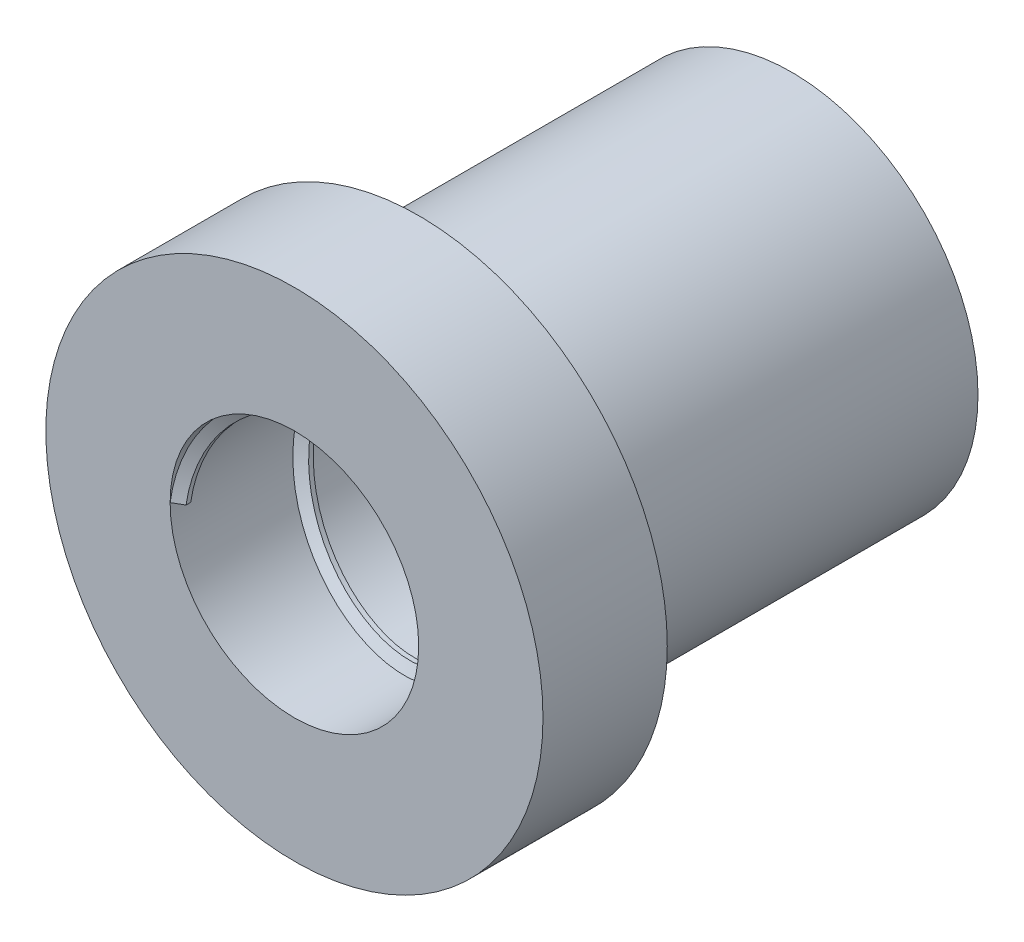
SolidWorks part; units mm, degrees
material "5052-H32"
ref_plane "Front Plane" through (0, 0, 0) normal (0, 0, 1) x (1, 0, 0)
ref_plane "Top Plane" through (0, 0, 0) normal (0, 1, 0) x (1, 0, 0)
ref_plane "Right Plane" through (0, 0, 0) normal (1, 0, 0) x (0, 0, -1)
sketch "Sketch1" plane through (0, 0, 0) normal (0, 0, 1) x (1, 0, 0)
  circle A0 centre (0, 0) radius 15
  circle A1 centre (0, 0) radius 10
  dimension "D1" = 30
  dimension "D2" = 20
extrude "Boss-Extrude1" add sketch "Sketch1" along normal blind 30
sketch "Sketch2" plane through (0, 0, 30) normal (0, 0, 1) x (1, 0, 0)
  circle A0 centre (0, 0) radius 20
  circle A1 centre (0, 0) radius 10
  dimension "D1" = 20
  dimension "D2" = 40
extrude "Boss-Extrude2" add sketch "Sketch2" along normal blind 10
thread "Thread1" pitch 1.5 method extrude profile "Thread Profile1" start angle 0, offset 0, length 40, pitch 10, diameter 20
ref_plane "Plane1" through (-10, 0, 40) normal (0, -1, 0) x (-1, 0, 0)
sketch "Thread Profile1" plane through (-10, 0, 40) normal (0, -1, 0) x (-1, 0, 0)
  line L0 (0, 0) -> (0, 1.5) construction
  line L11 (0, 0) -> (0, 1.3125)
  line L12 (0, 1.3125) -> (-0.8119, 0.8437)
  line L13 (-0.8119, 0.8437) -> (-0.8119, 0.4687)
  line L15 (-0.8119, 0.4687) -> (0, 0)
  line L17 (-0.8119, 0.6562) -> (0, 0.6562) construction
  point P2 (0, 0)
  dimension "Pitch" = 1.5
  dimension "Profile_Angle" = 60
  dimension "Profile_Land" = 0.375
  dimension "Profile_Height" = 0.8119
sketch "Sketch5" plane through (0, 0, 0) normal (1, 0, 0) x (0, 0, -1)
  line L0 (0, 15) -> (0, -15)
  line L1 (0, -15) -> (2.7575, -15)
  line L2 (2.7575, -15) -> (2.7575, 15)
  line L3 (2.7575, 15) -> (0, 15)
extrude "Cut-Extrude1" cut sketch "Sketch5" against normal blind 17 and the other way blind 16
